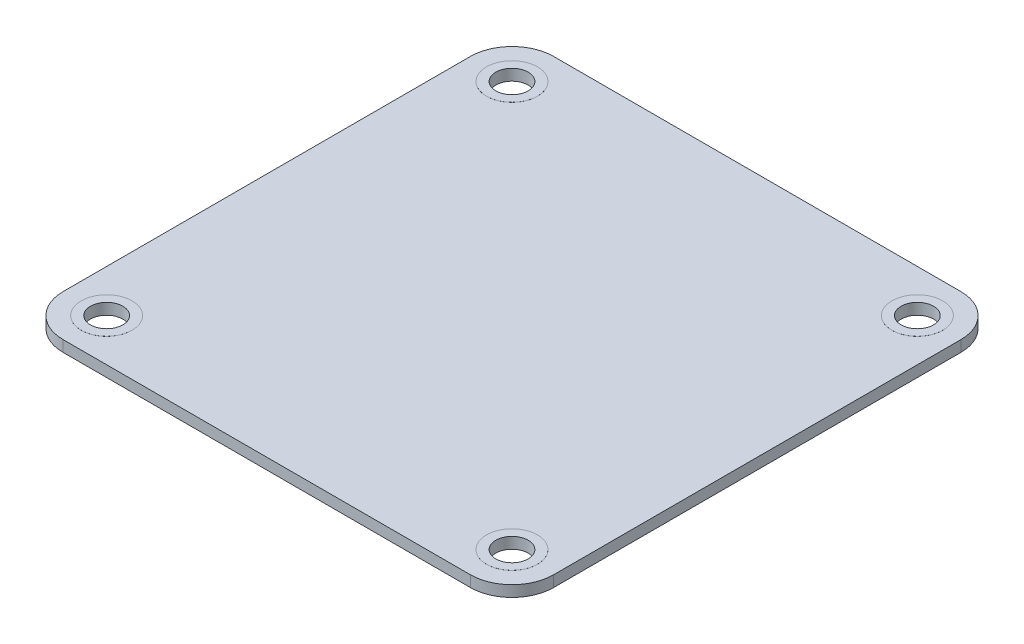
SolidWorks part; units mm, degrees
material "E-Glass Fiber"
ref_plane "Front Plane" through (0, 0, 0) normal (0, 0, 1) x (1, 0, 0)
ref_plane "Top Plane" through (0, 0, 0) normal (0, 1, 0) x (1, 0, 0)
ref_plane "Right Plane" through (0, 0, 0) normal (1, 0, 0) x (0, 0, -1)
sketch "Sketch1" plane through (0, 0, 0) normal (0, 1, 0) x (1, 0, 0)
  line L1 (22, -26.5) -> (-22, -26.5)
  line L2 (26.5, -22) -> (26.5, 22)
  line L3 (22, 26.5) -> (-22, 26.5)
  line L4 (-26.5, -22) -> (-26.5, 22)
  line L5 (26.5, -26.5) -> (-26.5, 26.5) construction
  line L6 (26.5, 26.5) -> (-26.5, -26.5) construction
  circle A0 centre (-21.9, 21.9) radius 1.755
  circle A1 centre (21.9, 21.9) radius 1.755
  circle A2 centre (-21.9, -21.9) radius 1.755
  circle A3 centre (21.9, -21.9) radius 1.755
  arc A4 (-26.5, 22) -> (-22, 26.5) centre (-22, 22) cw
  arc A5 (22, 26.5) -> (26.5, 22) centre (22, 22) cw
  arc A6 (26.5, -22) -> (22, -26.5) centre (22, -22) cw
  arc A7 (-22, -26.5) -> (-26.5, -22) centre (-22, -22) cw
  point P0 (0, 0)
  dimension "D3" = 3.51
  dimension "D5" = 4.5
  dimension "D1" = 53
  dimension "D2" = 53
  dimension "D4" = 43.8
extrude "Boss-Extrude1" add sketch "Sketch1" along normal blind 1.2
sketch "Sketch2" plane through (0, 0, 0) normal (0, 1, 0) x (1, 0, 0)
  circle A0 centre (-21.9, 21.9) radius 2.75
  circle A1 centre (21.9, 21.9) radius 2.75
  circle A2 centre (21.9, -21.9) radius 2.75
  circle A3 centre (-21.9, -21.9) radius 2.75
  circle A4 centre (-21.9, 21.9) radius 1.75
  circle A5 centre (21.9, 21.9) radius 1.75
  circle A6 centre (21.9, -21.9) radius 1.75
  circle A7 centre (-21.9, -21.9) radius 1.75
  dimension "D1" = 5.5
  dimension "D2" = 3.5
extrude "Boss-Extrude2" add sketch "Sketch2" along normal mid plane 1.21 from offset 0.6
